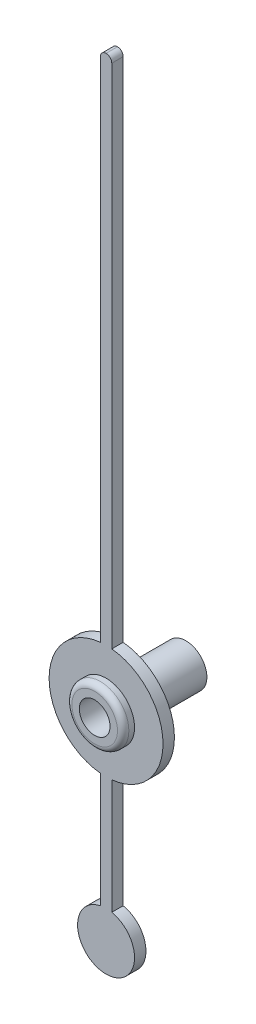
SolidWorks part; units mm, degrees
ref_plane "Alzado" through (0, 0, 0) normal (0, 0, 1) x (1, 0, 0)
ref_plane "Planta" through (0, 0, 0) normal (0, 1, 0) x (1, 0, 0)
ref_plane "Vista lateral" through (0, 0, 0) normal (1, 0, 0) x (0, 0, -1)
sketch "Sketch1" plane through (0, 0, 0) normal (0, 0, 1) x (1, 0, 0)
  line L0 (0, -1000) -> (0, 49000) construction
  line L1 (0.05, -999.9794) -> (0.05, 49000.0206) construction
  line L2 (-1000, 0) -> (49000, 0) construction
  line L3 (-999.9098, 5) -> (49000.0902, 5) construction
  line L4 (-1002.3398, -2) -> (48997.6602, -2) construction
  line L5 (-0.05, 5) -> (0.05, 5)
  line L6 (0.05, 5) -> (0.05, 0.4975)
  line L7 (0.05, -0.4975) -> (0.05, -1.5051)
  line L8 (-0.05, -0.4975) -> (-0.05, -1.5051)
  line L9 (-0.05, 5) -> (-0.05, 0.4975)
  arc A0 (0.05, -0.4975) -> (0.05, 0.4975) centre (0, 0) ccw
  arc A1 (-0.05, -1.5051) -> (0.05, -1.5051) centre (0, -1.75) ccw
  arc A2 (-0.05, 0.4975) -> (-0.05, -0.4975) centre (0, 0) ccw
  point P24 (0, 5)
  dimension "D1" = 1
  dimension "D5" = 0.5
  dimension "D2" = 5
  dimension "D3" = 2
  dimension "D4" = 0.05
extrude "Boss-Extrude1" add sketch "Sketch1" along normal blind 0.1
fillet "Fillet1" radius 0.05 2 edges at (-0.05, 5, 0.05) (0.05, 5, 0.05)
sketch "Sketch2" plane through (0, 0, 0) normal (0, 0, 1) x (1, 0, 0)
  circle A0 centre (0, 0) radius 0.25
  dimension "D1" = 0.5
extrude "Boss-Extrude2" add sketch "Sketch2" against normal blind 0.1 and the other way blind 0.2
sketch "Sketch3" plane through (0, 0, 0) normal (0, 0, 1) x (1, 0, 0)
  circle A0 centre (0, 0) radius 0.135
  dimension "D1" = 0.27
extrude "Cut-Extrude2" cut sketch "Sketch3" against normal through all both and the other way through all
fillet "Fillet2" radius 0.05 2 edges at (0.25, 0, -0.1) (0.25, 0, 0.2)
sketch "Sketch4" plane through (0, 0, -0.1) normal (0, 0, -1) x (-1, 0, 0)
  circle A0 centre (0, 0) radius 0.135 construction
  circle A1 centre (0, 0) radius 0.135
  circle A2 centre (0, 0) radius 0.185
  dimension "D1" = 0.05
extrude "Boss-Extrude3" add sketch "Sketch4" along normal blind 0.5
